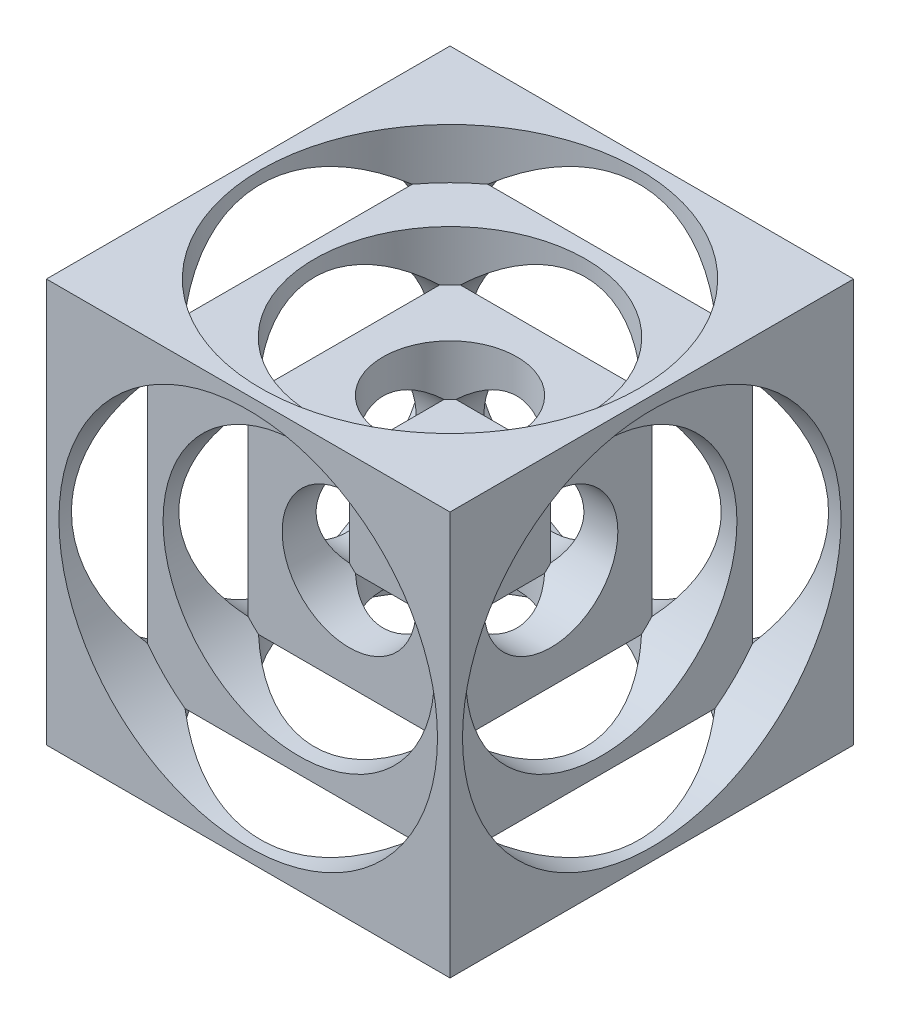
SolidWorks part; units mm, degrees
ref_plane "Front Plane" through (0, 0, 0) normal (0, 0, 1) x (1, 0, 0)
ref_plane "Top Plane" through (0, 0, 0) normal (0, 1, 0) x (1, 0, 0)
ref_plane "Right Plane" through (0, 0, 0) normal (1, 0, 0) x (0, 0, -1)
sketch "Sketch1" plane through (0, 0, 0) normal (0, 0, 1) x (1, 0, 0)
  line L1 (-22.86, -22.86) -> (22.86, -22.86)
  line L2 (-22.86, -22.86) -> (-22.86, 22.86)
  line L3 (-22.86, 22.86) -> (22.86, 22.86)
  line L4 (22.86, -22.86) -> (22.86, 22.86)
  line L5 (-22.86, -22.86) -> (22.86, 22.86) construction
  line L6 (-22.86, 22.86) -> (22.86, -22.86) construction
  point P0 (0, 0)
  dimension "D1" = 45.72
extrude "Boss-Extrude1" add sketch "Sketch1" against normal blind 22.86 and the other way blind 22.86
sketch "Sketch3" plane through (0, 0, 22.86) normal (0, 0, 1) x (1, 0, 0)
  line L1 (-5.715, -5.715) -> (5.715, -5.715)
  line L2 (-5.715, -5.715) -> (-5.715, 5.715)
  line L3 (-5.715, 5.715) -> (5.715, 5.715)
  line L4 (5.715, -5.715) -> (5.715, 5.715)
  line L5 (-5.715, -5.715) -> (5.715, 5.715) construction
  line L6 (-5.715, 5.715) -> (5.715, -5.715) construction
  line L7 (-11.43, -11.43) -> (11.43, -11.43)
  line L8 (-11.43, -11.43) -> (-11.43, 11.43)
  line L9 (-11.43, 11.43) -> (11.43, 11.43)
  line L10 (11.43, -11.43) -> (11.43, 11.43)
  line L11 (-11.43, -11.43) -> (11.43, 11.43) construction
  line L12 (-11.43, 11.43) -> (11.43, -11.43) construction
  line L13 (-17.145, -17.145) -> (17.145, -17.145)
  line L14 (-17.145, -17.145) -> (-17.145, 17.145)
  line L15 (-17.145, 17.145) -> (17.145, 17.145)
  line L16 (17.145, -17.145) -> (17.145, 17.145)
  line L17 (-17.145, -17.145) -> (17.145, 17.145) construction
  line L18 (-17.145, 17.145) -> (17.145, -17.145) construction
  point P0 (0, 0)
  point P6 (0, 0)
  point P11 (0, 0)
  dimension "D1" = 11.43
  dimension "D2" = 22.86
  dimension "D3" = 34.29
sketch "Sketch4" plane through (0, 0, 22.86) normal (0, 0, 1) x (1, 0, 0)
  circle A0 centre (0, 0) radius 7.5869
extrude "Cut-Extrude1" cut sketch "Sketch4" against normal blind 17.1704
sketch "Sketch5" plane through (0, 0, 22.86) normal (0, 0, 1) x (1, 0, 0)
  circle A0 centre (0, 0) radius 21.4424
extrude "Cut-Extrude2" cut sketch "Sketch5" against normal blind 5.715
sketch "Sketch6" plane through (0, 0, 22.86) normal (0, 0, 1) x (1, 0, 0)
  circle A0 centre (0, 0) radius 15.3621
extrude "Cut-Extrude3" cut sketch "Sketch6" against normal blind 11.43
sketch "Sketch8" plane through (0, 0, 5.6896) normal (0, 0, 1) x (1, 0, 0)
  circle A0 centre (0, 0) radius 5.5562
  dimension "D1" = 11.1125
ref_axis "Axis1" through (25.146, 0, 0) along (-1, 0, 0)
ref_axis "Axis2" through (0, -25.146, 0) along (0, 1, 0)
pattern_circular "CirPattern1" count 4 every 90 about axis through (0, -25.146, 0) along (0, 1, 0) of "Cut-Extrude3", "Cut-Extrude2", "Cut-Extrude1"
pattern_circular "CirPattern2" count 2 every 90 about axis through (25.146, 0, 0) along (-1, 0, 0) of "CirPattern1"
